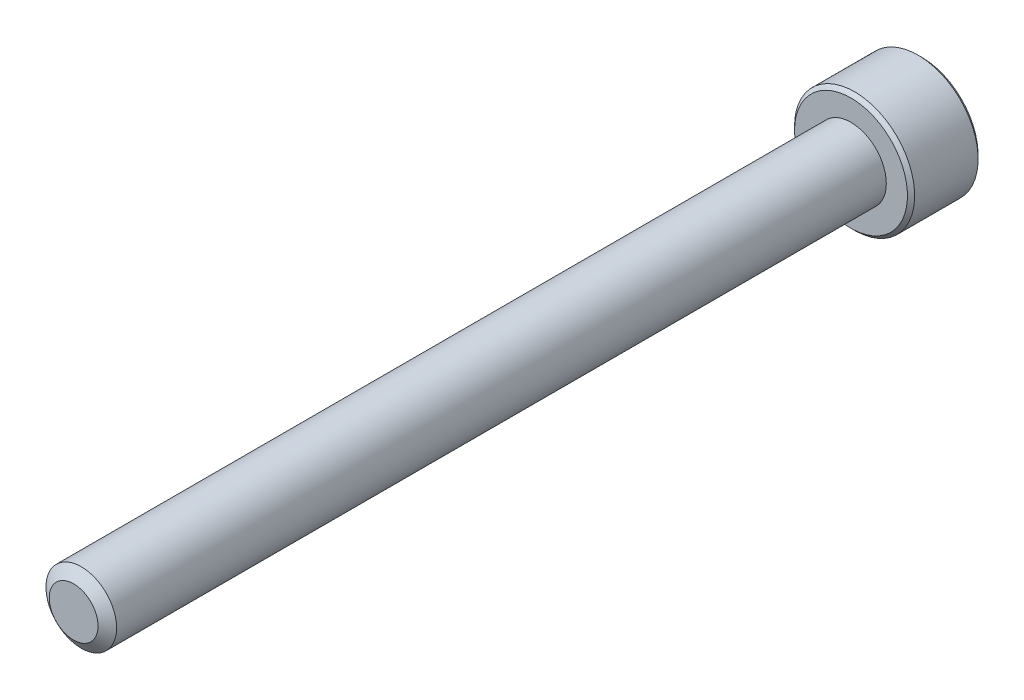
SolidWorks part; units mm, degrees
material "Alloy Steel"
ref_plane "Front Plane" through (0, 0, 0) normal (0, 0, 1) x (1, 0, 0)
ref_plane "Top Plane" through (0, 0, 0) normal (0, 1, 0) x (1, 0, 0)
ref_plane "Right Plane" through (0, 0, 0) normal (1, 0, 0) x (0, 0, -1)
sketch "Sketch1" plane through (0, 0, 0) normal (0, 0, 1) x (1, 0, 0)
  circle A0 centre (0, 0) radius 2.5
  dimension "OD" = 5
extrude "Extrude1" add sketch "Sketch1" against normal blind 55
sketch "Sketch2" plane through (0, 0, 0) normal (0, 0, 1) x (1, 0, 0)
  circle A0 centre (0, 0) radius 2.5 construction
  circle A1 centre (0, 0) radius 2.5
curve "Helix/Spiral1" [suppressed] pitch 0.8 height 55.8 turns 69.75 parameters "pitch"=0.8
sketch "Sketch3" plane through (0, 0, 0) normal (1, 0, 0) x (0, 0, -1)
  line L0 (-0.7, 2.5) -> (-0.4, 1.9804)
  line L1 (-0.4, 1.9804) -> (-0.3, 1.9804)
  line L2 (-0.3, 1.9804) -> (0, 2.5)
  line L3 (-0.7, 2.5) -> (0, 2.5)
  line L4 (-0.35, 2.5) -> (-0.35, 1.9804) construction
  line L5 (-0.55, 2.2402) -> (-0.15, 2.2402) construction
  line L6 (0, 2.5) -> (0, -2.5) construction
  line L7 (0, -2.5) -> (55, -2.5) construction
  point P11 (3.6, -2.5)
  dimension "D1" = 0.1
  dimension "D2" = 0.4
  dimension "D3" = 60
  dimension "D4" = 3.6
sweep "Cut-Sweep1" [suppressed] cut profiles "Sketch3" path "Helix/Spiral1"
sketch "Sketch4" plane through (0, 0, 0) normal (1, 0, 0) x (0, 0, -1)
  line L0 (0.5417, 2.5) -> (0, 1.7264)
  line L1 (0, 1.7264) -> (0, 2.5)
  line L2 (0.5417, 2.5) -> (0, 2.5)
  line L3 (-0.7, 2.5) -> (0, 2.5) construction
  line L4 (0, 0) -> (7.0209, 0) construction
  dimension "D1" = 55
  dimension "D2" = 0.254
revolve "Cut-Revolve1" cut sketch "Sketch4" angle 360 about L4
sketch "Sketch5" [suppressed] plane through (0, 0, 0) normal (1, 0, 0) x (0, 0, -1)
  line L0 (55, -2.3357) -> (55, 0) construction
  line L1 (55, 2.5) -> (22.1202, 2.5)
  line L2 (55, 2.5) -> (55, 0)
  line L3 (55, 0) -> (22, 0)
  line L4 (22, 2.1698) -> (22, 0)
  line L5 (22.1202, 2.5) -> (22, 2.1698)
  line L6 (0, 0) -> (9.9695, 0) construction
  point P3 (22, 2.5)
  point P10 (22, 2.5)
  dimension "D1" = 0.3302
  dimension "Thread min" = 22
  dimension "D3" = 20
revolve "partially thread" [suppressed] add sketch "Sketch5" angle 360 about L6
sketch "Sketch6" plane through (0, 0, -55) normal (0, 0, -1) x (-1, 0, 0)
  circle A0 centre (0, 0) radius 4.25
  dimension "head dia" = 8.5
extrude "Extrude2" add sketch "Sketch6" along normal blind 5
sketch "Sketch7" plane through (0, 0, -60) normal (0, 0, -1) x (-1, 0, 0)
  line L1 (0, 2.3094) -> (-2, 1.1547)
  line L2 (-2, 1.1547) -> (-2, -1.1547)
  line L3 (-2, -1.1547) -> (0, -2.3094)
  line L4 (0, -2.3094) -> (2, -1.1547)
  line L5 (2, -1.1547) -> (2, 1.1547)
  line L6 (2, 1.1547) -> (0, 2.3094)
  circle A0 centre (0, 0) radius 2 construction
  dimension "hex dia" = 4
extrude "Cut-Extrude1" cut sketch "Sketch7" against normal blind 3
sketch "Sketch8" plane through (0, 0, -60) normal (0, 0, -1) x (-1, 0, 0)
  circle A0 centre (0, 0) radius 2.3094
extrude "Cut-Extrude2" cut sketch "Sketch8" against normal through all draft 45
chamfer "Chamfer1" distance 0.255 angle 45 2 edges at (-4.25, 0, -60) (-4.25, 0, -55)
sketch "Sketch9" plane through (0, 0, 0) normal (1, 0, 0) x (0, 0, -1)
  line L0 (0, 2.5) -> (0, -2.5) construction
  line L1 (4.4, 2.5) -> (4.4, -2.5) construction
  dimension "D1" = 4.4
sketch "Sketch10" plane through (0, 0, 0) normal (1, 0, 0) x (0, 0, -1)
  line L0 (55, 2.5) -> (55, 0)
  line L1 (55, 2.5) -> (54.8, 2.5)
  line L2 (54.8, 2.5) -> (53.7645, 0)
  line L3 (55, 0) -> (53.7645, 0)
  line L4 (55, 3.995) -> (55, -3.995) construction
  dimension "D1" = 22.5
  dimension "D2" = 0.2
revolve "Revolve1" add sketch "Sketch10" angle 360 about L3
equation "\"D3@Helix/Spiral1\" = \"screw length@Extrude1\"+\"pitch@Helix/Spiral1\""
equation "\"D1@Sketch3\" = \"pitch@Helix/Spiral1\"*.125"
equation "\"D2@Sketch3\" = \"pitch@Helix/Spiral1\"*.5"
equation "\"D1@Cut-Extrude1\" = \"hex dia@Sketch7\"*.75"
equation "\"D1@Chamfer1\" = \"head dia@Sketch6\"*.03"
equation "\"D1@Sketch9\" = \"pitch@Helix/Spiral1\"*5.5"
equation "\"D2@Sketch10\" = \"pitch@Helix/Spiral1\"*.25"
equation "\"D4@Sketch3\" = \"pitch@Helix/Spiral1\"*4.50"
